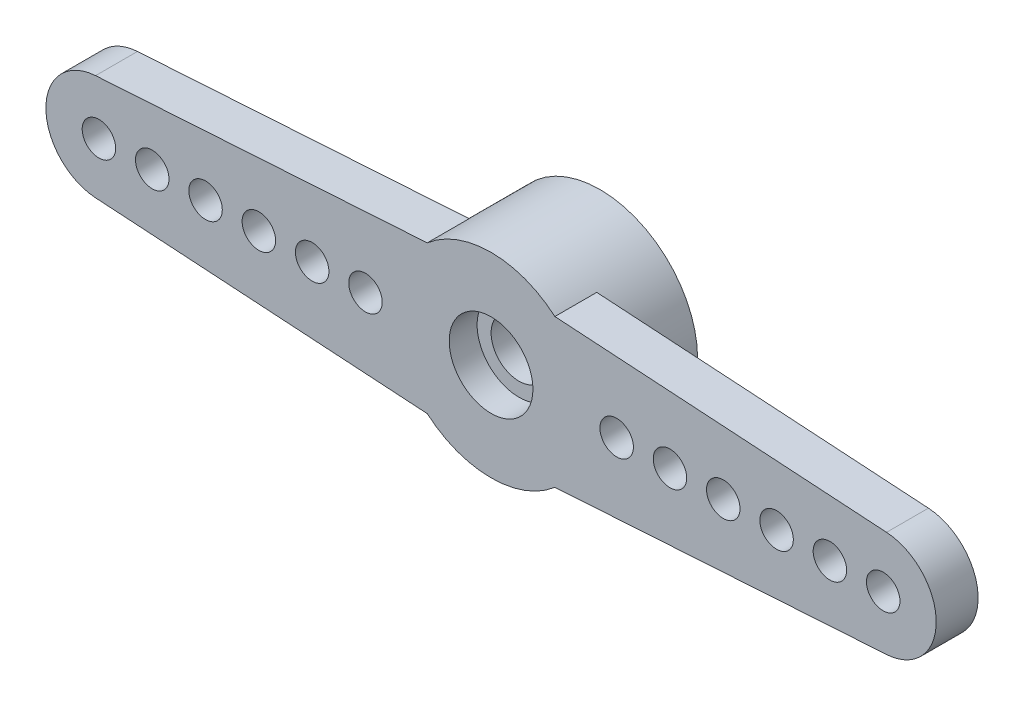
SolidWorks part; units mm, degrees
ref_plane "前视基准面" through (0, 0, 0) normal (0, 0, 1) x (1, 0, 0)
ref_plane "上视基准面" through (0, 0, 0) normal (0, 1, 0) x (1, 0, 0)
ref_plane "右视基准面" through (0, 0, 0) normal (1, 0, 0) x (0, 0, -1)
other "Configuration Table"
sketch "草图1" plane through (0, 0, 0) normal (0, 0, 1) x (1, 0, 0)
  line L12 (15.95, 15.99) -> (15.95, -15.1175) construction
  line L13 (0, 0) -> (14.05, 0) construction
  line L14 (2.2864, 2.65) -> (14.1703, 1.8962)
  line L15 (14.1703, -1.8962) -> (2.2864, -2.65)
  line L16 (2.2864, 2.65) -> (2.2864, -2.65)
  line L17 (4.5, 0) -> (6.41, 0)
  line L18 (6.41, 0) -> (8.32, 0)
  line L19 (8.32, 0) -> (10.23, 0)
  line L20 (10.23, 0) -> (12.14, 0)
  line L21 (12.14, 0) -> (14.05, 0)
  line L22 (-3.5, 5.9995) -> (-3.5, -4.0704) construction
  line L23 (4.5, 6.4068) -> (4.5, 4.4679) construction
  circle A0 centre (0, 0) radius 3.5
  circle A1 centre (0, 0) radius 1.5
  circle A2 centre (0, 0) radius 1
  circle A3 centre (0, 0) radius 2.5
  circle A4 centre (14.05, 0) radius 1.9
  circle A5 centre (14.05, 0) radius 0.6
  circle A6 centre (4.5, 0) radius 0.6
  circle A7 centre (6.41, 0) radius 0.6
  circle A8 centre (8.32, 0) radius 0.6
  circle A9 centre (10.23, 0) radius 0.6
  circle A10 centre (12.14, 0) radius 0.6
  dimension "D1" = 7
  dimension "D2" = 5
  dimension "D3" = 2
  dimension "D4" = 3
  dimension "D6" = 3.8
  dimension "D8" = 1.2
  dimension "D5" = 15.95
  dimension "D7" = 5.3
  dimension "D9" = 8
extrude "凸台-拉伸1" add sketch "草图1" along normal blind 3.9 contours A0
extrude "凸台-拉伸2" add sketch "草图1<6>" against normal blind 1.5 from surface contours A10 A4 L14 A0 L15 A9 A8 A7 A6 | A10 A5 A4 region at (8.2201, 2.1432, 0) region at (15.3967, 1.264, 0) starting at face at (3.5, 0, 3.9)
sketch "草图1<6>" plane through (0, 0, 0) normal (0, 0, 1) x (1, 0, 0) same geometry as "草图1"
mirror "镜向1" about plane through (0, 0, 0) normal (1, 0, 0) of "凸台-拉伸2"
extrude "切除-拉伸1" cut sketch "草图1<3>" along normal blind 2 contours A3
sketch "草图1<3>" plane through (0, 0, 0) normal (0, 0, 1) x (1, 0, 0) same geometry as "草图1"
extrude "切除-拉伸2" cut sketch "草图1<4>" against normal blind 1 from surface contours A1 starting at face at (0, 0, 3.9)
sketch "草图1<4>" plane through (0, 0, 0) normal (0, 0, 1) x (1, 0, 0) same geometry as "草图1"
extrude "切除-拉伸3" cut sketch "草图1<5>" along normal through all contours A2
sketch "草图1<5>" plane through (0, 0, 0) normal (0, 0, 1) x (1, 0, 0) same geometry as "草图1"
